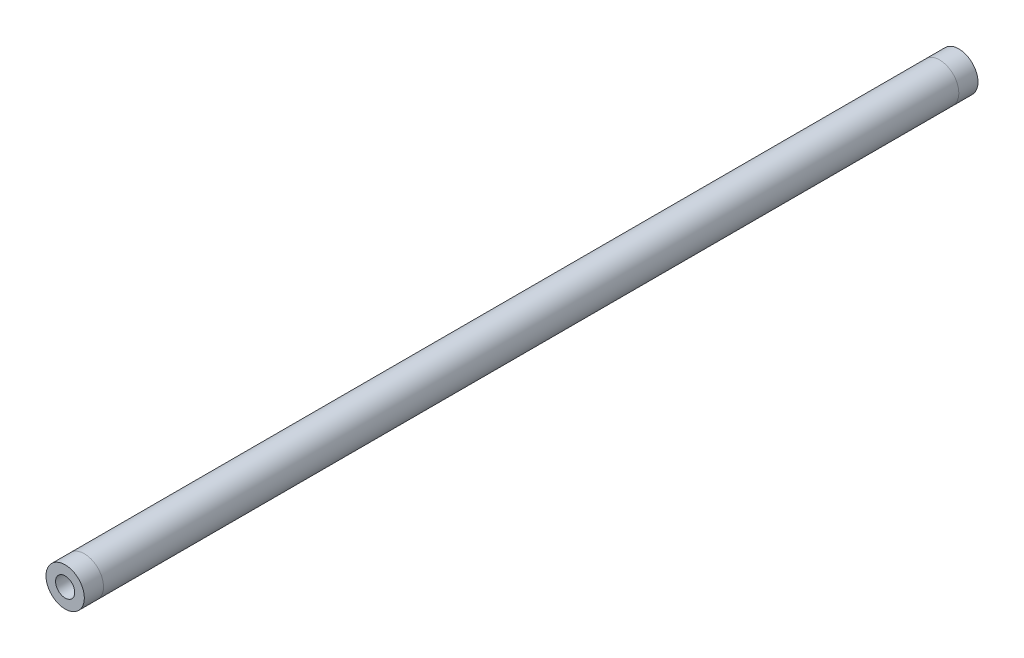
SolidWorks part; units mm, degrees
material "AISI 4130 Steel, normalized at 870C"
ref_plane "Front Plane" through (0, 0, 0) normal (0, 0, 1) x (1, 0, 0)
ref_plane "Top Plane" through (0, 0, 0) normal (0, 1, 0) x (1, 0, 0)
ref_plane "Right Plane" through (0, 0, 0) normal (1, 0, 0) x (0, 0, -1)
sketch "Axis" plane through (0, 0, 0) normal (0, 1, 0) x (1, 0, 0)
  line L0 (0, 0) -> (0, 21.9075) construction
  line L1 (0, 21.9075) -> (0, 317.7011) construction
  line L2 (0, 317.7011) -> (0, 339.6086) construction
  dimension "D1" = 21.9075
  dimension "D2" = 339.6086
sketch "Sketch2" plane through (0, 0, 0) normal (0, 0, 1) x (1, 0, 0)
  circle A0 centre (0, 0) radius 6.35
  circle A1 centre (0, 0) radius 3.175
  circle A2 centre (0, 0) radius 4.7625
  dimension "D1" = 12.7
  dimension "D2" = 6.35
  dimension "D3" = 9.525
extrude "Threaded Insert 1-1" add sketch "Sketch2" against normal blind 6.35 from vertex contours A0 A2 | A2 A1 region at (-6.1704, 0, 0) region at (-4.6278, 0, 0) starting at point (0, 0, -21.9075)
extrude "Threaded Insert 1-2" add sketch "Sketch2<5>" against normal blind 6.35 from surface contours A2 A1 region at (-4.6278, 0, 0) starting at face at (6.35, 0, -28.2575)
sketch "Sketch2<5>" plane through (0, 0, 0) normal (0, 0, 1) x (1, 0, 0) same geometry as "Sketch2"
extrude "Boss-Extrude4" add sketch "Sketch2<7>" along normal blind 6.35 from vertex separate body contours A0 A2 | A2 A1 region at (-6.1704, 0, 0) region at (-4.6278, 0, 0) starting at point (0, 0, -317.7011)
sketch "Sketch2<7>" plane through (0, 0, 0) normal (0, 0, 1) x (1, 0, 0) same geometry as "Sketch2"
extrude "Boss-Extrude5" add sketch "Sketch2<8>" along normal blind 6.35 from surface contours A2 A1 region at (-4.6278, 0, 0) starting at face at (6.35, 0, -311.3511)
sketch "Sketch2<8>" plane through (0, 0, 0) normal (0, 0, 1) x (1, 0, 0) same geometry as "Sketch2"
extrude "Boss-Extrude6" add sketch "Sketch2<9>" against normal up to surface (311.3511 mm away) from surface separate body contours A0 A2 region at (-6.1704, 0, 0) up to face at (6.35, 0, -311.3511) starting at face at (4.7625, 0, -28.2575)
sketch "Sketch2<9>" plane through (0, 0, 0) normal (0, 0, 1) x (1, 0, 0) same geometry as "Sketch2"
move or copy body "Body-Move/Copy1" [suppressed] bodies to move or copy 102 105 106 parameters "D1"=0, "D2"=0, "D3"=0
equation "\"Tube Outer Diameter\"= .5"
equation "\"Tube Inner Diameter\"= .375"
equation "\"Rod end Diameter\"= .25"
equation "\"Threaded Insert Out\"= .25"
equation "\"Threaded Insert In\"= .25'`"
equation "\"D1@Sketch2\"=\"Tube Outer Diameter\""
equation "\"D2@Sketch2\"=\"Rod end Diameter\""
equation "\"D1@Threaded Insert 1-1\" = \"Threaded Insert Out\""
equation "\"D3@Sketch2\"=\"Tube Inner Diameter\""
equation "\"D1@Threaded Insert 1-2\" = \"Threaded Insert In\""
equation "\"D1@Boss-Extrude4\"=\"Threaded Insert Out\""
equation "\"D1@Boss-Extrude5\"=\"Threaded Insert In\""
